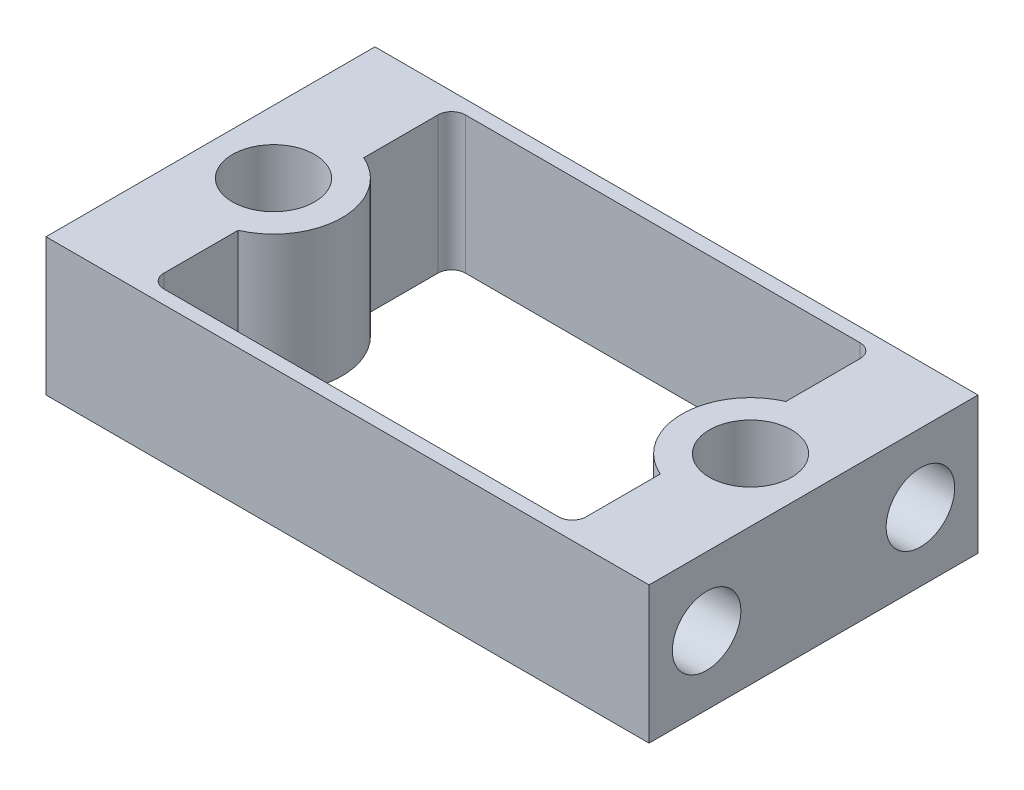
SolidWorks part; units mm, degrees
ref_plane "Front Plane" through (0, 0, 0) normal (0, 0, 1) x (1, 0, 0)
ref_plane "Top Plane" through (0, 0, 0) normal (0, 1, 0) x (1, 0, 0)
ref_plane "Right Plane" through (0, 0, 0) normal (1, 0, 0) x (0, 0, -1)
sketch "Sketch1" plane through (0, 0, 0) normal (0, 1, 0) x (1, 0, 0)
  line L1 (-11, 6) -> (11, 6)
  line L2 (-11, 6) -> (-11, -6)
  line L3 (-11, -6) -> (11, -6)
  line L4 (11, 6) -> (11, -6)
  line L5 (-11, 6) -> (11, -6) construction
  line L6 (-11, -6) -> (11, 6) construction
  point P0 (0, 0)
  dimension "D1" = 22
  dimension "D2" = 12
extrude "Boss-Extrude1" add sketch "Sketch1" along normal blind 5
sketch "Sketch2" plane through (0, 5, 0) normal (0, 1, 0) x (1, 0, 0)
  line L0 (8.7, -3.7) -> (8.7, -1.5) construction
  line L2 (-8.7, 3.7) -> (-8.7, 1.5) construction
  line L4 (11, -6) -> (11, 6)
  line L5 (11, 6) -> (-11, 6)
  line L6 (-11, 6) -> (-11, -6)
  line L7 (-11, -6) -> (11, -6)
  line L8 (11, -6) -> (11, 6) construction
  line L9 (11, 6) -> (-11, 6) construction
  line L10 (-11, 6) -> (-11, -6) construction
  line L11 (-11, -6) -> (11, -6) construction
  line L12 (-8.7, -1.5) -> (-8.7, -3.7) construction
  line L13 (-8.7, 3.7) -> (-8.7, -3.7) construction
  line L14 (8.7, 1.5) -> (8.7, 3.7) construction
  line L15 (8.7, -3.7) -> (8.7, 3.7) construction
  line L16 (7.7, -5.5) -> (7.7, -2.2913)
  line L18 (-7.7, -2.2913) -> (-7.7, -5.5)
  line L19 (-7.7, 5.5) -> (-7.7, 2.2913)
  line L21 (7.7, 2.2913) -> (7.7, 5.5)
  line L22 (-7.7, 5.5) -> (7.7, 5.5)
  line L23 (8.7, 3.7) -> (-8.7, 3.7) construction
  line L24 (-7.7, -5.5) -> (7.7, -5.5)
  line L25 (-8.7, -3.7) -> (8.7, -3.7) construction
  line L26 (-11, -6) -> (11, -6) construction
  arc A0 (-8.7, -1.5) -> (-8.7, 1.5) centre (-8.7, 0) ccw construction
  arc A1 (8.7, 1.5) -> (8.7, -1.5) centre (8.7, 0) ccw construction
  arc A2 (7.7, 2.2913) -> (7.7, -2.2913) centre (8.7, 0) ccw
  arc A3 (-7.7, -2.2913) -> (-7.7, 2.2913) centre (-8.7, 0) ccw
  point P11 (-7.2, 0)
  point P15 (-11, 0)
  point P18 (-7.7, -3.1754)
  point P28 (-7.6796, -5)
  dimension "D3" = 3
  dimension "D4" = 17.4
  dimension "D9" = 1
  dimension "D10" = 1
  dimension "D2" = 17.4
  dimension "D5" = 1
  dimension "D6" = 1
  dimension "D7" = 0.5
  dimension "D8" = 0.5
  dimension "D1" = 0
hole_wizard "M3 Clearance Hole1" positions "Sketch3" profile "Sketch4" hole size "M3" standard "ANSI Metric" end condition through all
sketch "Sketch3" plane through (0, 5, 0) normal (0, 1, 0) x (1, 0, 0)
  point P0 (-8.7, 0)
  point P3 (8.7, 0)
sketch "Sketch4" plane through (-8.7, 5, 0) normal (1, 0, 0) x (0, 0, 1)
  line L0 (0, 0) -> (0, 5)
  line L1 (0, 5) -> (1.5, 5)
  line L2 (1.5, 5) -> (1.5, 0)
  line L5 (1.5, 0) -> (0, 0)
  line L11 (0, -6.35) -> (0, 107.95) construction
  dimension "Thru Hole Dia." = 3
  dimension "Thru Hole Depth" = 5
extrude "Cut-Extrude1" cut sketch "Sketch2" against normal through all
sketch "Sketch5" plane through (11, 0, 0) normal (1, 0, 0) x (0, 0, -1)
  line L0 (-3.9, 2.5) -> (3.9, 2.5) construction
  line L1 (-6, 5) -> (6, 5) construction
  line L2 (6, 5) -> (6, 0) construction
  point P0 (-3.9, 2.5)
  point P1 (3.9, 2.5)
  point P6 (0, 5)
  point P7 (0, 2.5)
  point P8 (0, 0)
  point P11 (6, 2.5)
  dimension "D1" = 7.8
hole_wizard "M3x0.5 Tapped Hole2" positions "Sketch6" profile "Sketch7" tap size "M3x0.5" standard "ANSI Metric" end condition up to next
sketch "Sketch6" plane through (11, 0, 0) normal (1, 0, 0) x (0, 0, -1)
  point P0 (-3.9, 2.5)
  point P3 (3.9, 2.5)
sketch "Sketch7" plane through (11, 2.5, 3.9) normal (0, 1, 0) x (0, 0, -1)
  line L0 (0, 0) -> (0, 3.3)
  line L1 (0, 3.3) -> (1.25, 3.3)
  line L2 (1.25, 3.3) -> (1.25, 0)
  line L5 (1.25, 0) -> (0, 0)
  line L11 (0, -6.35) -> (0, 107.95) construction
  dimension "Thru Tap Drill Dia." = 2.5
  dimension "Thru Tap Drill Depth" = 3.3
cosmetic thread "Hole Thread3" parameters "D2"=3
cosmetic thread "Hole Thread4" parameters "D2"=3
fillet "Fillet1" radius 0.5 4 edges at (7.7, 2.5, 5.5) (7.7, 2.5, -5.5) (-7.7, 2.5, -5.5) (-7.7, 2.5, 5.5)
